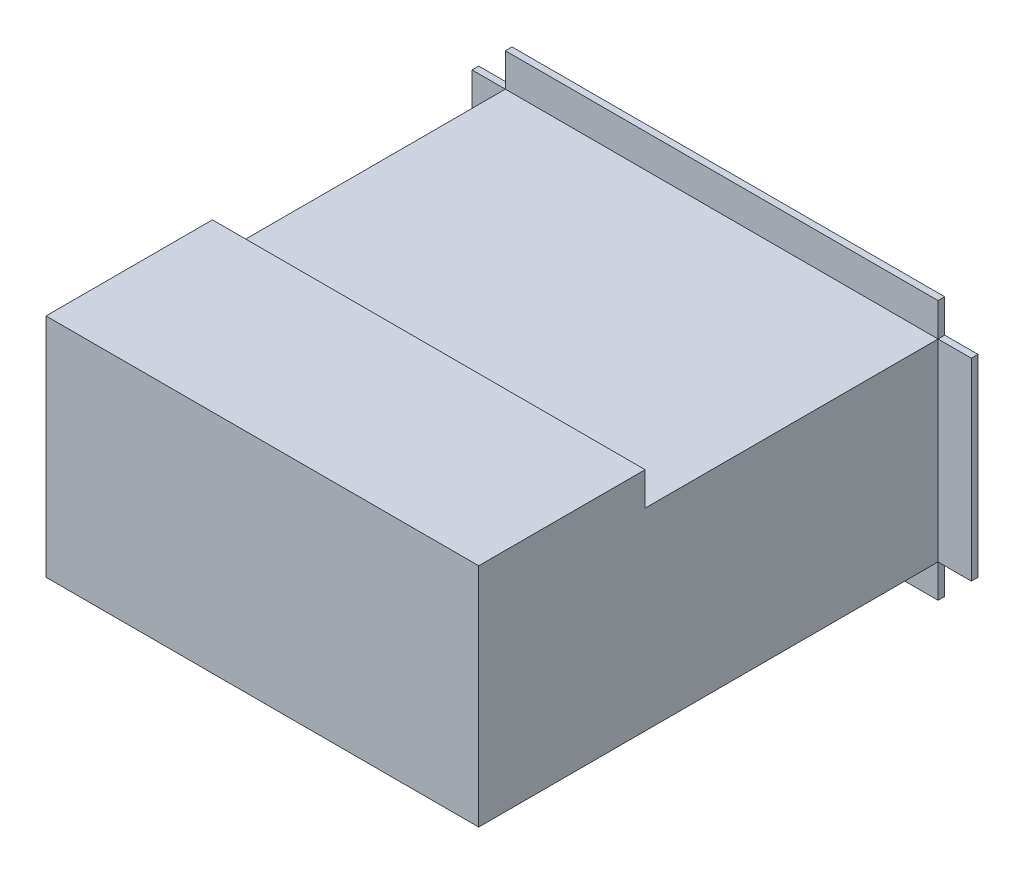
SolidWorks part; units mm, degrees
ref_plane "前视基准面" through (0, 0, 0) normal (0, 0, 1) x (1, 0, 0)
ref_plane "上视基准面" through (0, 0, 0) normal (0, 1, 0) x (1, 0, 0)
ref_plane "右视基准面" through (0, 0, 0) normal (1, 0, 0) x (0, 0, -1)
sketch "草图1" plane through (0, 0, 0) normal (0, 0, 1) x (1, 0, 0)
  line L0 (-10.3053, 0) -> (10.73, 0) construction
  line L1 (-6.5, 3.4) -> (6.5, 3.4)
  line L2 (-6.5, 3.4) -> (-6.5, -3.4)
  line L3 (-6.5, -3.4) -> (6.5, -3.4)
  line L4 (6.5, 3.4) -> (6.5, -3.4)
  line L5 (0, 6.9027) -> (0, -6.4151) construction
  dimension "D1" = 13
  dimension "D2" = 6.8
extrude "拉伸1" add sketch "草图1" along normal blind 14
sketch "草图3" plane through (0, 3.4, 0) normal (0, 1, 0) x (-1, 0, 0)
  line L0 (6.5, 14) -> (6.5, 0) construction
  line L1 (6.5, 0.2) -> (-6.5, 0.2)
  line L2 (6.5, 0.2) -> (6.5, 9)
  line L3 (6.5, 9) -> (-6.5, 9)
  line L4 (-6.5, 0.2) -> (-6.5, 9)
  line L5 (-6.5, 14) -> (-6.5, 0) construction
  line L6 (-6.5, 0) -> (6.5, 0) construction
  dimension "D1" = 0.2
  dimension "D2" = 9
extrude "切除-拉伸1" cut sketch "草图3" against normal blind 1
sketch "草图4" plane through (0, 0, 0) normal (0, 0, -1) x (-1, 0, 0)
  line L0 (0, 4.4975) -> (0, -5.9453) construction
  line L1 (-6.5, 2.4) -> (6.5, 2.4) construction
  line L2 (-7.5, 2.4) -> (7.5, 2.4)
  line L3 (-7.5, 2.4) -> (-7.5, -3.401)
  line L4 (-7.5, -3.401) -> (-6.5, -3.4)
  line L8 (-6.5, -3.4) -> (-6.5, -4.4)
  line L10 (-6.5, -4.4) -> (6.5, -4.4)
  line L11 (6.5, -4.4) -> (6.5, -3.4)
  line L13 (6.5, -3.4) -> (7.5, -3.4)
  line L14 (7.5, -3.4) -> (7.5, 2.4)
  line L15 (-6.5, -3.4) -> (-6.5, 3.4) construction
  line L16 (6.5, -3.4) -> (-6.5, -3.4) construction
  dimension "D1" = 1
  dimension "D2" = 1
  dimension "D3" = 1
extrude "拉伸2" add sketch "草图4" against normal blind 0.2
sketch "草图6" plane through (0, 0, 0) normal (0, 0, -1) x (-1, 0, 0)
  line L8 (0, -5.8737) -> (0, 5.0433) construction
  line L9 (6.3, -3.2) -> (6.3, 2.2)
  line L10 (-6.3, -3.2) -> (6.3, -3.2)
  line L11 (-6.3, 2.2) -> (-6.3, -3.2)
  line L12 (6.3, 2.2) -> (-6.3, 2.2)
  line L13 (6.3, -3.2) -> (6.3, 2.2)
  line L14 (-6.3, -3.2) -> (6.3, -3.2)
  line L15 (-6.3, 2.2) -> (-6.3, -3.2)
  line L16 (6.3, 2.2) -> (-6.3, 2.2)
  dimension "D1" = 0.2
extrude "切除-拉伸2" cut sketch "草图6" against normal up to surface (9 mm away) up to face at (0, 2.9, 9)
sketch "草图7" plane through (0, 0, 9) normal (0, 0, -1) x (-1, 0, 0)
  line L0 (0, 4.6551) -> (0, -5.5647) construction
  line L1 (-5, -0.2) -> (5, -0.2)
  line L2 (-5, -0.2) -> (-5, -2.2)
  line L3 (-5, -2.2) -> (5, -2.2)
  line L4 (5, -0.2) -> (5, -2.2)
  line L5 (-6.3, -3.2) -> (6.3, -3.2) construction
  dimension "D1" = 1
  dimension "D2" = 2
  dimension "D3" = 10
extrude "拉伸3" add sketch "草图7" along normal offset from surface (8.5 mm away) 0.5 up to face at (0, -0.5, 0)
chamfer "倒角1" distance 0.5 angle 45 4 edges at (0, -0.2, 0.5) (5, -1.2, 0.5) (0, -2.2, 0.5) (-5, -1.2, 0.5)
